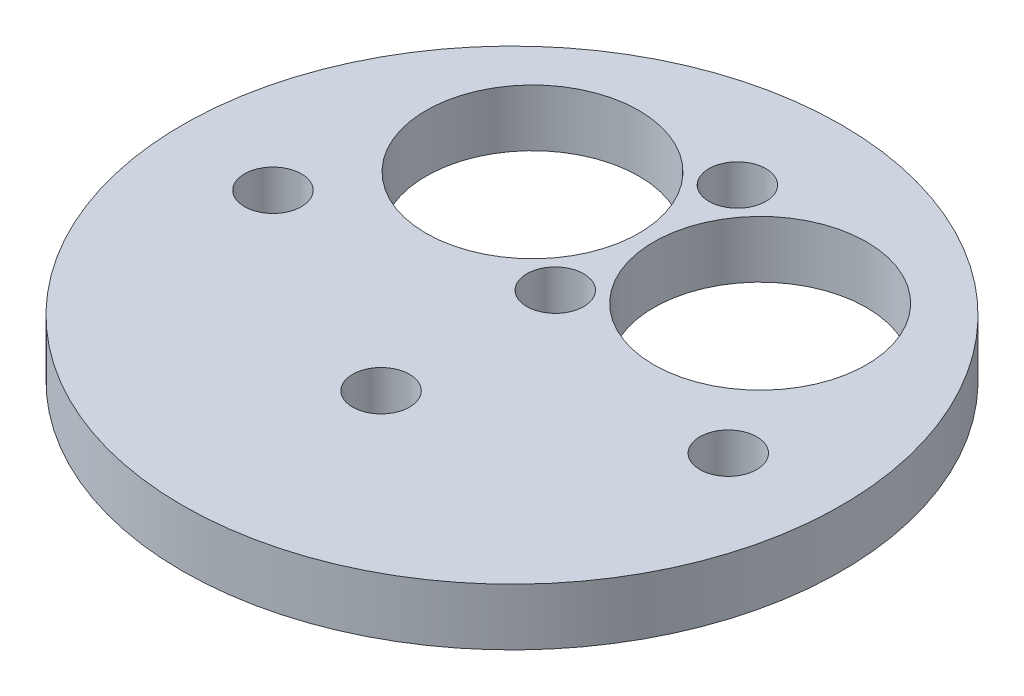
SolidWorks part; units mm, degrees
material "G10 Fiberglass"
ref_plane "Front Plane" through (0, 0, 0) normal (0, 0, 1) x (1, 0, 0)
ref_plane "Top Plane" through (0, 0, 0) normal (0, 1, 0) x (1, 0, 0)
ref_plane "Right Plane" through (0, 0, 0) normal (1, 0, 0) x (0, 0, -1)
ref_axis "Axis1" through (0, 55, 0) along (0, -1, 0)
sketch "Sketch1" plane through (0, 0, 0) normal (0, 0, 1) x (1, 0, 0)
  line L0 (0, 0) -> (36.7665, 0)
  line L3 (36.7665, 0) -> (36.7665, 6.35)
  line L4 (36.7665, 6.35) -> (0, 6.35)
  line L5 (0, 55) -> (0, -55) construction
  line L6 (0, 6.35) -> (0, 0)
  line L7 (0, 0) -> (0, 21.2966) construction
  dimension "D1" = 73.533
  dimension "D2" = 6.35
revolve "Revolve1" add sketch "Sketch1" angle 360 about L7
sketch "Sketch2" plane through (0, 6.35, 0) normal (0, 1, 0) x (1, 0, 0)
  line L0 (-12.7, 14.986) -> (12.7, 14.986) construction
  line L1 (0, 25.146) -> (0, 4.826) construction
  line L2 (-12.7, 14.986) -> (12.7, 14.986) construction
  line L3 (-12.7, 28.956) -> (12.7, 28.956) construction
  line L4 (-12.7, 1.016) -> (12.7, 1.016) construction
  circle A0 centre (-12.7, 14.986) radius 11.8745
  circle A1 centre (0, 0) radius 36.7665
  circle A3 centre (12.7, 14.986) radius 11.8745
  circle A4 centre (0, 25.146) radius 3.175
  circle A5 centre (0, 4.826) radius 3.175
  arc A6 (-12.7, 28.956) -> (-12.7, 1.016) centre (-12.7, 14.986) ccw construction
  arc A7 (12.7, 1.016) -> (12.7, 28.956) centre (12.7, 14.986) ccw construction
  circle A8 centre (0, -14.605) radius 3.175
  circle A9 centre (0, 0) radius 34.163 construction
  circle A11 centre (0, 0) radius 36.7665 construction
  point P11 (0, 14.986)
  point P12 (0, 14.986)
  point P15 (0, 14.986)
  dimension "D2" = 23.749
  dimension "D3" = 23.749
  dimension "D5" = 6.35
  dimension "D6" = 6.35
  dimension "D11" = 6.35
  dimension "D4" = 25.4
  dimension "D7" = 20.32
  dimension "D8" = 25.4
  dimension "D9" = 27.94
  dimension "D10" = 14.605
  dimension "D12" = 1.016
  dimension "D1" = 0
extrude "Cut-Extrude1" cut sketch "Sketch2" against normal through all both and the other way through all
sketch "Sketch3" plane through (0, 6.35, 0) normal (0, 1, 0) x (1, 0, 0)
  line L0 (-25.4, -1.27) -> (25.4, -1.27) construction
  circle A0 centre (-25.4, -1.27) radius 3.175
  circle A1 centre (25.4, -1.27) radius 3.175
  point P4 (0, -1.27)
  dimension "D1" = 6.35
  dimension "D2" = 6.35
  dimension "D3" = 50.8
  dimension "D4" = 1.27
extrude "Cut-Extrude2" cut sketch "Sketch3" against normal through all both
ref_plane "Plane1" through (0, 3.175, 0) normal (0, 1, 0) x (-1, 0, 0)
equation "\"D3@Sketch2\"=\"D2@Sketch2\""
equation "\"D6@Sketch2\"=\"D5@Sketch2\""
